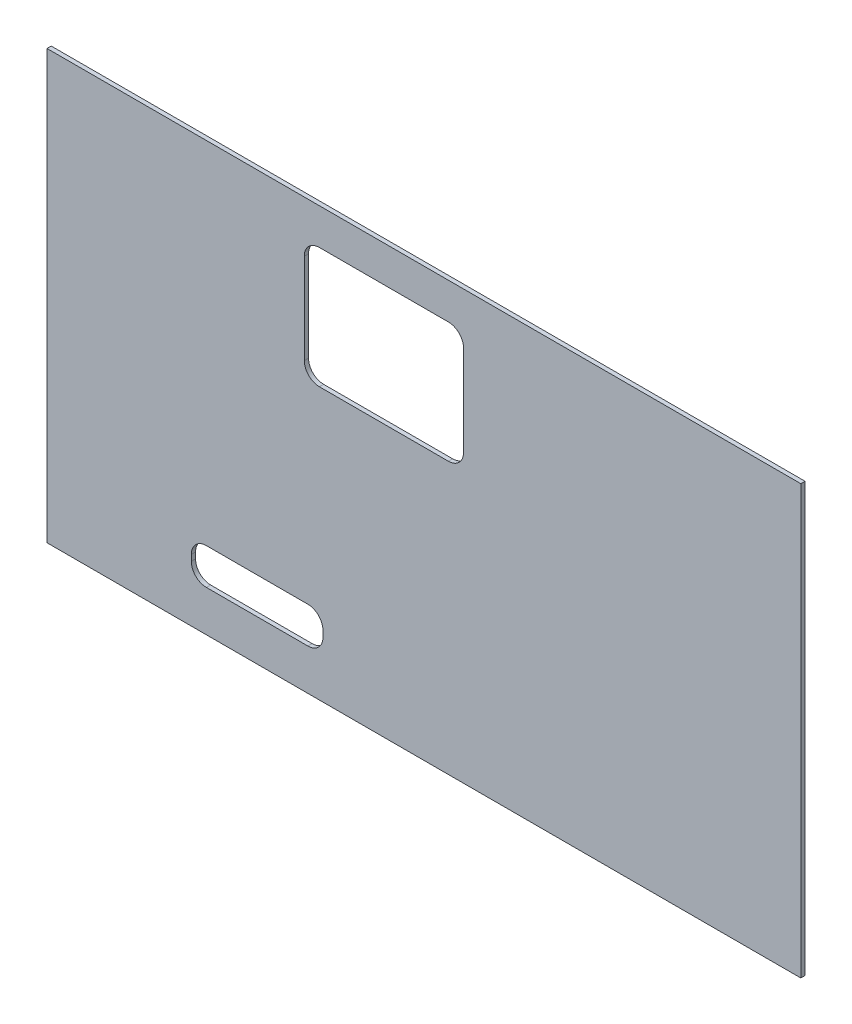
SolidWorks part; units mm, degrees
ref_plane "Front Plane" through (0, 0, 0) normal (0, 0, 1) x (1, 0, 0)
ref_plane "Top Plane" through (0, 0, 0) normal (0, 1, 0) x (1, 0, 0)
ref_plane "Right Plane" through (0, 0, 0) normal (1, 0, 0) x (0, 0, -1)
sketch "Sketch2" plane through (0, 0, 0) normal (0, 0, 1) x (1, 0, 0)
  line L0 (9, -6) -> (19, -6)
  line L1 (0, 0) -> (125.0228, 0)
  line L2 (0, 0) -> (0, -71)
  line L3 (0, -71) -> (125.0228, -71)
  line L4 (125.0228, 0) -> (125.0228, -71)
  line L5 (9, -6) -> (14, -18)
  line L6 (14, -18) -> (19, -6)
  line L7 (4, -6) -> (4, -17)
  line L8 (4, -17) -> (11.25, -34.4)
  line L9 (11.25, -34.4) -> (11.25, -23.4)
  line L10 (11.25, -23.4) -> (4, -6)
  line L11 (24, -6) -> (24, -17)
  line L12 (24, -17) -> (16.75, -34.4)
  line L13 (16.75, -34.4) -> (16.75, -23.4)
  line L14 (16.75, -23.4) -> (24, -6)
  line L15 (24, -6) -> (42.6775, -6)
  line L16 (0, 0) -> (4, 0)
  line L17 (0, 0) -> (0, -6)
  line L20 (16.75, -58.1932) -> (16.75, -71)
  line L21 (16.75, -58.1932) -> (23.9424, -58.1932)
  line L22 (23.9424, -58.1932) -> (45.7691, -58.1932)
  line L23 (23.9424, -58.1932) -> (23.9424, -64.1932)
  line L24 (23.9424, -64.1932) -> (45.7691, -64.1932)
  line L25 (45.7691, -64.1932) -> (45.7691, -58.1932)
  line L26 (42.6775, -6) -> (69.0876, -6)
  line L27 (42.6775, -6) -> (42.6775, -26)
  line L28 (42.6775, -26) -> (69.0876, -26)
  line L29 (69.0876, -26) -> (69.0876, -6)
  line L30 (69.0876, -6) -> (100.1386, -6)
  line L31 (112.8886, -34.4) -> (112.8886, -23.4)
  line L32 (100.1386, -17) -> (107.3886, -34.4)
  line L33 (105.1386, -6) -> (110.1386, -18)
  line L34 (100.1386, -6) -> (100.1386, -17)
  line L35 (120.1386, -17) -> (112.8886, -34.4)
  line L36 (120.1386, -6) -> (120.1386, -17)
  line L37 (107.3886, -23.4) -> (100.1386, -6)
  line L38 (105.1386, -6) -> (115.1386, -6)
  line L39 (112.8886, -23.4) -> (120.1386, -6)
  line L40 (110.1386, -18) -> (115.1386, -6)
  line L41 (107.3886, -34.4) -> (107.3886, -23.4)
  line L42 (113.1386, -33.15) -> (113.1386, -23.45)
  line L43 (113.1386, -23.45) -> (119.8886, -7.25)
  line L44 (119.8886, -7.25) -> (119.8886, -16.95)
  line L45 (119.8886, -16.95) -> (113.1386, -33.15)
  line L46 (100.3886, -16.95) -> (107.1386, -33.15)
  line L47 (107.1386, -33.15) -> (107.1386, -23.45)
  line L48 (107.1386, -23.45) -> (100.3886, -7.25)
  line L49 (100.3886, -7.25) -> (100.3886, -16.95)
  line L50 (105.5136, -6.25) -> (110.1386, -17.35)
  line L51 (110.1386, -17.35) -> (114.7636, -6.25)
  line L52 (105.5136, -6.25) -> (114.7636, -6.25)
  line L53 (9.375, -6.25) -> (18.625, -6.25)
  line L54 (14, -17.35) -> (18.625, -6.25)
  line L55 (9.375, -6.25) -> (14, -17.35)
  line L56 (4.25, -7.25) -> (4.25, -16.95)
  line L57 (4.25, -16.95) -> (11, -33.15)
  line L58 (11, -33.15) -> (11, -23.45)
  line L59 (11, -23.45) -> (4.25, -7.25)
  line L60 (23.75, -7.25) -> (23.75, -16.95)
  line L61 (23.75, -16.95) -> (17, -33.15)
  line L62 (17, -33.15) -> (17, -23.45)
  line L63 (17, -23.45) -> (23.75, -7.25)
  point P8 (14, -6)
  point P17 (0, 0)
  point P20 (16.75, -58.1932)
  point P35 (110.1386, -6)
  dimension "D1" = 125.0228
  dimension "D2" = 71
  dimension "D3" = 10
  dimension "D4" = 11
  dimension "D5" = 0.25
  dimension "D7" = 18.6775
  dimension "D8" = 12.8068
  dimension "D9" = 7.1924
  dimension "D10" = 21.8267
  dimension "D11" = 6
  dimension "D12" = 26.4101
  dimension "D13" = 20
  dimension "D14" = 31.051
  dimension "D15" = 10
  dimension "D16" = 11
extrude "Boss-Extrude5" add sketch "Sketch2" along normal blind 0.7 contours L25 L24 L23 L3 L4 L1 L2 L22 L41 L32 L34 L29 L28 L27 L11 L12 L13 L14 L26 L37 L40 L33 L38 L10 L9 L8 L7 L6 L5 L0 L31 L39 L36 L35 | L14 L13 L12 L11 L62 L63 L60 L61 | L9 L10 L7 L8 L59 L58 L57 L56 | L5 L6 L0 L55 L53 L54 | L39 L31 L35 L36 L44 L45 L42 L43 | L33 L40 L38 L50 L52 L51 | L32 L41 L37 L34 L49 L48 L47 L46 | L53 L54 L55 | L56 L57 L58 L59 | L60 L61 L62 L63 | L50 L51 L52 | L42 L43 L44 L45 | L46 L47 L48 L49 region at (14, -6.1562, 0) region at (63.4521, -37.4124, 0) region at (7.5979, -14.7113, 0) region at (23.9707, -11.5, 0) region at (103.7366, -14.7113, 0) region at (112.9179, -28.9, 0) region at (110.1386, -6.1562, 0)
extrude "Boss-Extrude6" add sketch "Sketch2<9>" against normal blind 5 contours L53 L55 L54 | L63 L62 L61 L60 | L58 L59 L56 L57 | L48 L49 L46 L47 | L52 L50 L51 | L45 L44 L43 L42 region at (116.5136, -20.2, 0) region at (103.7636, -20.2, 0) region at (110.1386, -9.95, 0) region at (14, -9.95, 0) region at (7.625, -20.2, 0) region at (20.375, -20.2, 0)
sketch "Sketch2<9>" plane through (0, 0, 0) normal (0, 0, 1) x (1, 0, 0) same geometry as "Sketch2"
fillet "Fillet1" radius 2.5 8 edges at (23.9424, -64.1932, 0.35) (45.7691, -64.1932, 0.35) (45.7691, -58.1932, 0.35) (23.9424, -58.1932, 0.35) (42.6775, -6, 0.35) (69.0876, -6, 0.35) (42.6775, -26, 0.35) (69.0876, -26, 0.35)
